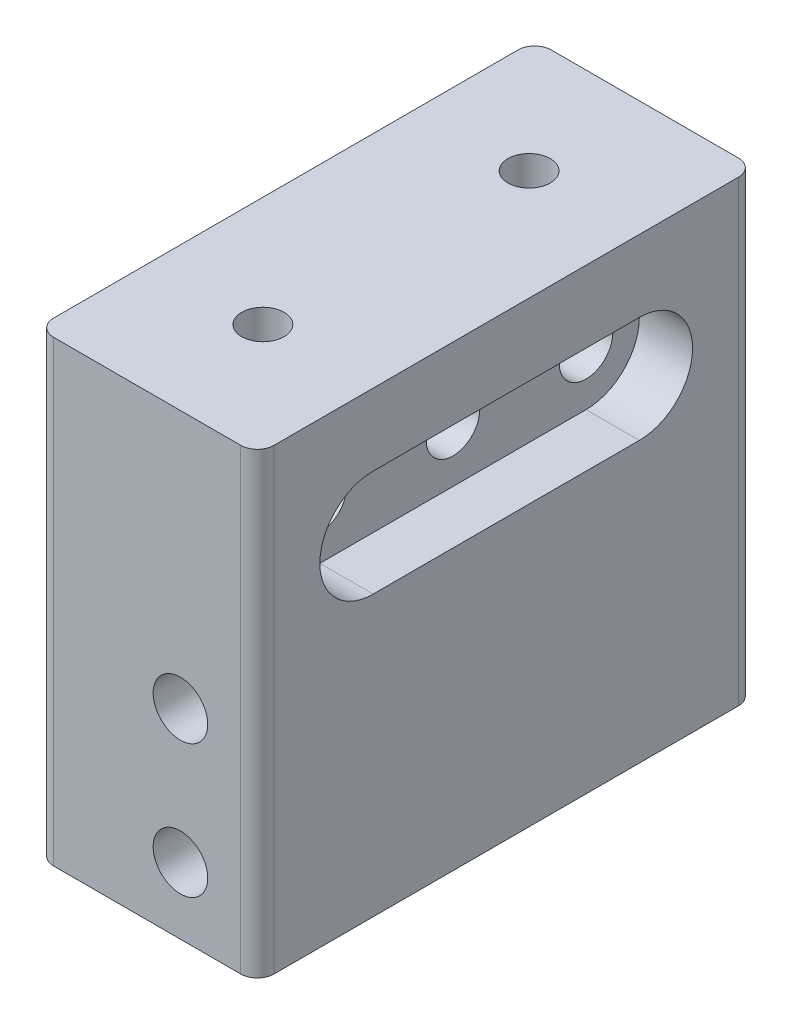
SolidWorks part; units mm, degrees
material "Nylon 101"
ref_plane "Front Plane" through (0, 0, 0) normal (0, 0, 1) x (1, 0, 0)
ref_plane "Top Plane" through (0, 0, 0) normal (0, 1, 0) x (1, 0, 0)
ref_plane "Right Plane" through (0, 0, 0) normal (1, 0, 0) x (0, 0, -1)
sketch "Sketch1" plane through (0, 0, 0) normal (0, 1, 0) x (1, 0, 0)
  line L1 (-10.5156, -23.7427) -> (10.5156, -23.7427)
  line L2 (-10.5156, -23.7427) -> (-10.5156, 23.7426)
  line L3 (-10.5156, 23.7426) -> (10.5156, 23.7426)
  line L4 (10.5156, -23.7427) -> (10.5156, 23.7426)
  line L5 (-10.5156, -23.7427) -> (10.5156, 23.7426) construction
  line L6 (-10.5156, 23.7426) -> (10.5156, -23.7427) construction
  point P0 (0, 0)
  dimension "D1" = 21.0312
  dimension "D2" = 47.4853
extrude "Boss-Extrude1" add sketch "Sketch1" along normal mid plane 38.1
sketch "Sketch2" plane through (0, 0, 23.7427) normal (0, 0, 1) x (1, 0, 0)
  line L5 (-10.5156, 19.05) -> (10.5156, 19.05) construction
  circle A1 centre (3.175, -12.7) radius 2.6035
  circle A2 centre (3.175, 0) radius 2.6035
  dimension "D3" = 19.05
  dimension "D1" = 7.3406
  dimension "D2" = 5.207
  dimension "D4" = 12.7
extrude "Cut-Extrude1" cut sketch "Sketch2" against normal through all
sketch "Sketch4" plane through (10.5156, 0, 0) normal (1, 0, 0) x (0, 0, -1)
  line L0 (-23.7427, 19.05) -> (23.7426, 19.05) construction
  circle A0 centre (-12.7, 12.7) radius 2.5527
  circle A1 centre (12.7, 12.7) radius 2.5527
  circle A2 centre (0, 12.7) radius 2.5527
  dimension "D5" = 5.1054
  dimension "D1" = 6.35
  dimension "D3" = 12.7
  dimension "D4" = 12.7
extrude "Cut-Extrude3" cut sketch "Sketch4" against normal through all
fillet "Fillet1" radius 1.5875 4 edges at (10.5156, 0, 23.7427) (-10.5156, 0, 23.7427) (-10.5156, 0, -23.7426) (10.5156, 0, -23.7426)
sketch "Sketch7" plane through (10.5156, 0, 0) normal (1, 0, 0) x (0, 0, -1)
  line L0 (-12.7, 12.7) -> (12.7, 12.7) construction
  line L1 (-12.7, 17.78) -> (12.7, 17.78)
  line L2 (-12.7, 7.62) -> (12.7, 7.62)
  arc A0 (-12.7, 17.78) -> (-12.7, 7.62) centre (-12.7, 12.7) ccw
  arc A1 (12.7, 7.62) -> (12.7, 17.78) centre (12.7, 12.7) ccw
  point P4 (0, 12.7)
  dimension "D1" = 5.08
extrude "Cut-Extrude5" cut sketch "Sketch7" against normal blind 5.08
sketch "Sketch8" plane through (0, 19.05, 0) normal (0, 1, 0) x (1, 0, 0)
  line L4 (-8.9281, -23.7427) -> (8.9281, -23.7427)
  line L5 (10.5156, -22.1552) -> (10.5156, 22.1551)
  line L6 (8.9281, 23.7426) -> (-8.9281, 23.7426)
  line L7 (-10.5156, 22.1551) -> (-10.5156, -22.1552)
  line L8 (-8.9281, -23.7427) -> (8.9281, -23.7427)
  line L9 (10.5156, -22.1552) -> (10.5156, 22.1551)
  line L10 (8.9281, 23.7426) -> (-8.9281, 23.7426)
  line L11 (-10.5156, 22.1551) -> (-10.5156, -22.1552)
  arc A4 (8.9281, -23.7427) -> (10.5156, -22.1552) centre (8.9281, -22.1552) ccw
  arc A5 (10.5156, 22.1551) -> (8.9281, 23.7426) centre (8.9281, 22.1551) ccw
  arc A6 (-8.9281, 23.7426) -> (-10.5156, 22.1551) centre (-8.9281, 22.1551) ccw
  arc A7 (-8.9281, 23.7426) -> (-10.5156, 22.1551) centre (-8.9281, 22.1551) ccw
  arc A8 (8.9281, -23.7427) -> (10.5156, -22.1552) centre (8.9281, -22.1552) ccw
  arc A9 (10.5156, 22.1551) -> (8.9281, 23.7426) centre (8.9281, 22.1551) ccw
  arc A10 (-10.5156, -22.1552) -> (-8.9281, -23.7427) centre (-8.9281, -22.1552) ccw
  arc A11 (-10.5156, -22.1552) -> (-8.9281, -23.7427) centre (-8.9281, -22.1552) ccw
  dimension "D1" = 0
extrude "Boss-Extrude2" add sketch "Sketch8" along normal blind 5.588
sketch "Sketch9" plane through (0, 24.638, 0) normal (0, 1, 0) x (1, 0, 0)
  line L0 (-10.5156, 0) -> (10.5156, 0) construction
  line L1 (-10.5156, 22.1551) -> (-10.5156, -22.1552) construction
  line L2 (10.5156, -22.1552) -> (10.5156, 22.1551) construction
  circle A0 centre (0, 12.7) radius 2.0193
  circle A2 centre (0, -12.7) radius 2.0193
  dimension "D2" = 4.0386
  dimension "D1" = 12.7
  dimension "D3" = 10.5156
extrude "Cut-Extrude6" cut sketch "Sketch9" against normal blind 5.08
